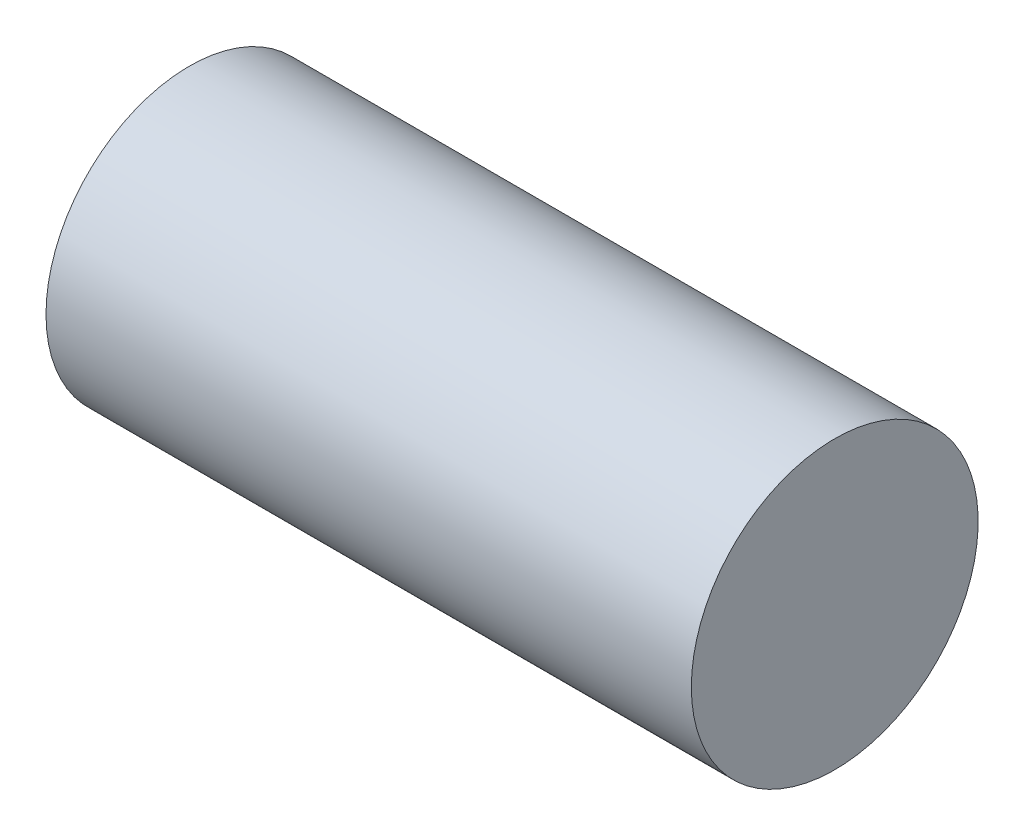
SolidWorks part; units mm, degrees
ref_plane "Front Plane" through (0, 0, 0) normal (0, 0, 1) x (1, 0, 0)
ref_plane "Top Plane" through (0, 0, 0) normal (0, 1, 0) x (1, 0, 0)
ref_plane "Right Plane" through (0, 0, 0) normal (1, 0, 0) x (0, 0, -1)
sketch "Hose_End_6 Sketch" plane through (0, 0, 0) normal (0, 0, 1) x (1, 0, 0)
  line L0 (-1000, 0) -> (1000, 0) construction
  line L1 (0, 0) -> (0, 10)
  line L2 (0, 10) -> (45, 10)
  line L3 (45, 10) -> (45, 0)
  line L4 (45, 0) -> (0, 0)
revolve "Hose_End_6" add sketch "Hose_End_6 Sketch" angle 360 about L0
ref_axis "Engine Axis" through (47.25, 0, 0) along (-1, 0, 0)
sketch "Socket 1 Sketch" plane through (0, 0, 0) normal (0, 0, 1) x (1, 0, 0)
  line L0 (-1000, 0) -> (1000, 0) construction
  line L1 (-1, 0) -> (-1, 4.7625)
  line L2 (-1, 4.7625) -> (16.8, 4.7625)
  line L3 (16.8, 4.7625) -> (16.8, 0)
  line L4 (16.8, 0) -> (-1, 0)
revolve "Socket 1" cut sketch "Socket 1 Sketch" angle 360 about L0
